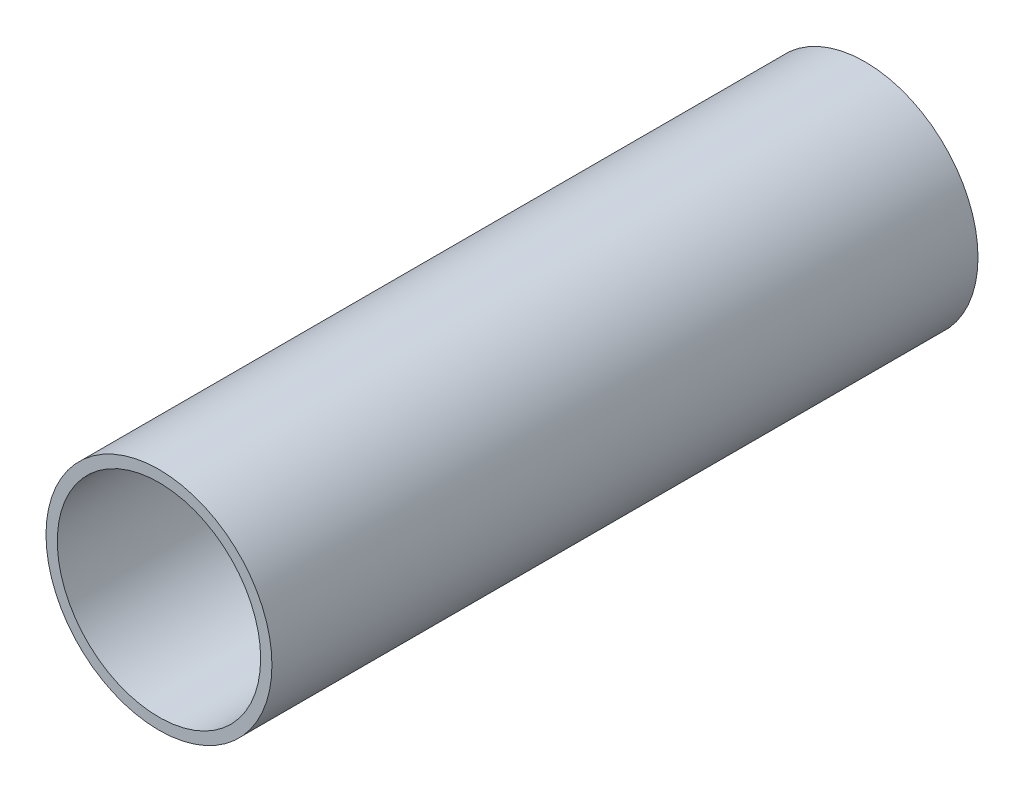
SolidWorks part; units mm, degrees
ref_plane "Front Plane" through (0, 0, 0) normal (0, 0, 1) x (1, 0, 0)
ref_plane "Top Plane" through (0, 0, 0) normal (0, 1, 0) x (1, 0, 0)
ref_plane "Right Plane" through (0, 0, 0) normal (1, 0, 0) x (0, 0, -1)
sketch "Sketch1" plane through (0, 0, 0) normal (0, 0, 1) x (1, 0, 0)
  circle A0 centre (0, 0) radius 18
  circle A1 centre (0, 0) radius 20
  dimension "D1" = 36
  dimension "D2" = 40
extrude "Boss-Extrude1" add sketch "Sketch1" along normal blind 125
